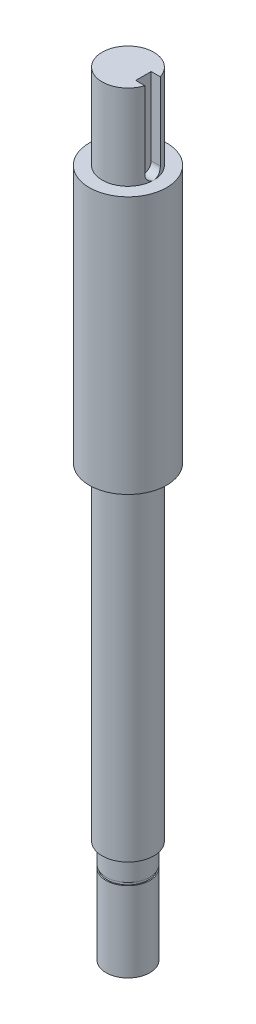
SolidWorks part; units mm, degrees
ref_plane "Front Plane" through (0, 0, 0) normal (0, 0, 1) x (1, 0, 0)
ref_plane "Top Plane" through (0, 0, 0) normal (0, 1, 0) x (1, 0, 0)
ref_plane "Right Plane" through (0, 0, 0) normal (1, 0, 0) x (0, 0, -1)
sketch "Sketch1" plane through (0, 0, 0) normal (1, 0, 0) x (0, 0, -1)
  line L0 (0, 24) -> (0, -276) construction
  line L1 (0, 24) -> (10, 24)
  line L2 (10, 24) -> (10, -9)
  line L3 (10, -9) -> (15, -9)
  line L4 (15, -9) -> (15, -109)
  line L5 (15, -109) -> (10, -109)
  line L6 (10, -109) -> (10, -236)
  line L7 (10, -236) -> (8.5, -236)
  line L8 (8.5, -236) -> (8.5, -243.9)
  line L9 (8.5, -276) -> (0, -276)
  line L10 (0, 24) -> (0, -276)
  line L11 (8.5, -243.9) -> (8.1, -243.9)
  line L12 (8.1, -243.9) -> (8.1, -245)
  line L13 (8.1, -245) -> (8.5, -245)
  line L14 (8.5, -245) -> (8.5, -276)
  dimension "D1" = 20
  dimension "D2" = 30
  dimension "D3" = 100
  dimension "D4" = 9
  dimension "D5" = 20
  dimension "D6" = 17
  dimension "D7" = 40
  dimension "D8" = 300
  dimension "D9" = 33
  dimension "D10" = 1.1
  dimension "D11" = 8.1
  dimension "D12" = 9
revolve "Revolve1" add sketch "Sketch1" angle 360 about L0
sketch "Sketch2" plane through (0, 0, 0) normal (1, 0, 0) x (0, 0, -1)
  line L0 (0, 24) -> (0, -6) construction
  line L1 (3, 24) -> (3, -6)
  line L2 (-3, 24) -> (-3, -6)
  line L3 (10, -9) -> (-10, -9) construction
  line L4 (10, 24) -> (-10, 24) construction
  arc A0 (3, 24) -> (-3, 24) centre (0, 24) ccw
  arc A1 (-3, -6) -> (3, -6) centre (0, -6) ccw
  point P3 (0, 9)
  dimension "D1" = 6
extrude "Cut-Extrude1" cut sketch "Sketch2" along normal through all from offset 6
equation "\"d_ext_rouleau\"= 90"
equation "\"epaisseur_rouleau\"=80"
equation "\"alesage-rouleau\"= 52"
equation "\"jeu_dent_rouleau\"= 2"
equation "\"profondeur_dent_rouleau\"=4"
equation "\"n_dent_roueau\"= 15"
equation "\"d_ext_roulement_rouleau\"= 42"
equation "\"d_int_roulement_rouleau\"= 20"
equation "\"B_roulement_rouleau\"= 12"
equation "\"r_roulement_rouleau\"= 0.6"
equation "\"d_bille_roulement_rouleau\"= 8"
equation "\"F_anneau_alesage_rouleau\"=1.85"
equation "\"G_anneau_alesage_rouleau\"=47.5"
equation "\"K_anneau_alesage_rouleau\"=3.75"
equation "\"d_vis_flasque_rouleau\"=5"
equation "\"l-x_vis_flasque_rouleau\"=4"
equation "\"g_anneau_arbre_rouleau\"=19"
equation "\"f_anneau_arbre_rouleau\"=1.3"
equation "\"k_anneau_arbre_rouleau\"=1.5"
equation "\"h_matrice\"= 18"
equation "\"d_matrice\"= 220"
equation "\"d_granulat\"= 8"
equation "\"zone_vide_matrice\" = 48"
equation "\"d_alesage_matrice\"=20"
equation "\"a_clavette_alesage_matrice\"=6"
equation "\"entrax_vis_rouleau\"=65"
equation "\"B_roulement_matrice\"= 12"
equation "\"d_ext_roulement_matrice\"= 42"
equation "\"d_int_roulement_matrice\"= 20"
equation "\"r_roulement_matrice\"= 1"
equation "\"D1@Sketch1\"=\"d_int_roulement_matrice\""
equation "\"D2@Sketch1\"=\"d_int_roulement_matrice\"+10"
equation "\"h_epaulement_arbre_matrice\" = 100"
equation "\"D3@Sketch1\"=\"h_epaulement_arbre_matrice\""
equation "\"D4@Sketch1\"=\"h_matrice\"/2"
equation "\"h_polie_matrice\" = 40"
equation "\"D7@Sketch1\"=\"h_polie_matrice\""
equation "\"l_arbre_matrice\" = 300"
equation "\"D8@Sketch1\"=\"l_arbre_matrice\""
equation "\"D9@Sketch1\"=\"h_matrice\"+15"
equation "\"D1@Sketch2\"=\"a_clavette_alesage_matrice\""
equation "\"D19@Cut-Extrude1\"=\"j_clavette_arbre_matrice\""
equation "\"j_clavette_arbre_matrice\" = 6"
equation "\"D5@Sketch1\"=\"d_int_roulement_matrice\""
equation "\"D6@Sketch1\"=\"d_int_roulement_matrice\"-3"
equation "\"f_anneaux_arbre_matrice\" = 1.1"
equation "\"D10@Sketch1\"=\"f_anneaux_arbre_matrice\""
equation "\"g_anneaux_arbre_matrice\" = 16.2"
equation "\"D11@Sketch1\"=\"g_anneaux_arbre_matrice\"/2"
equation "\"B_roulement_bc_arbre_matrice\"= 10"
equation "\"e_anneaux_arbre_matrice\" = 1"
equation "\"D12@Sketch1\"=\"B_roulement_bc_arbre_matrice\"-\"e_anneaux_arbre_matrice\""
